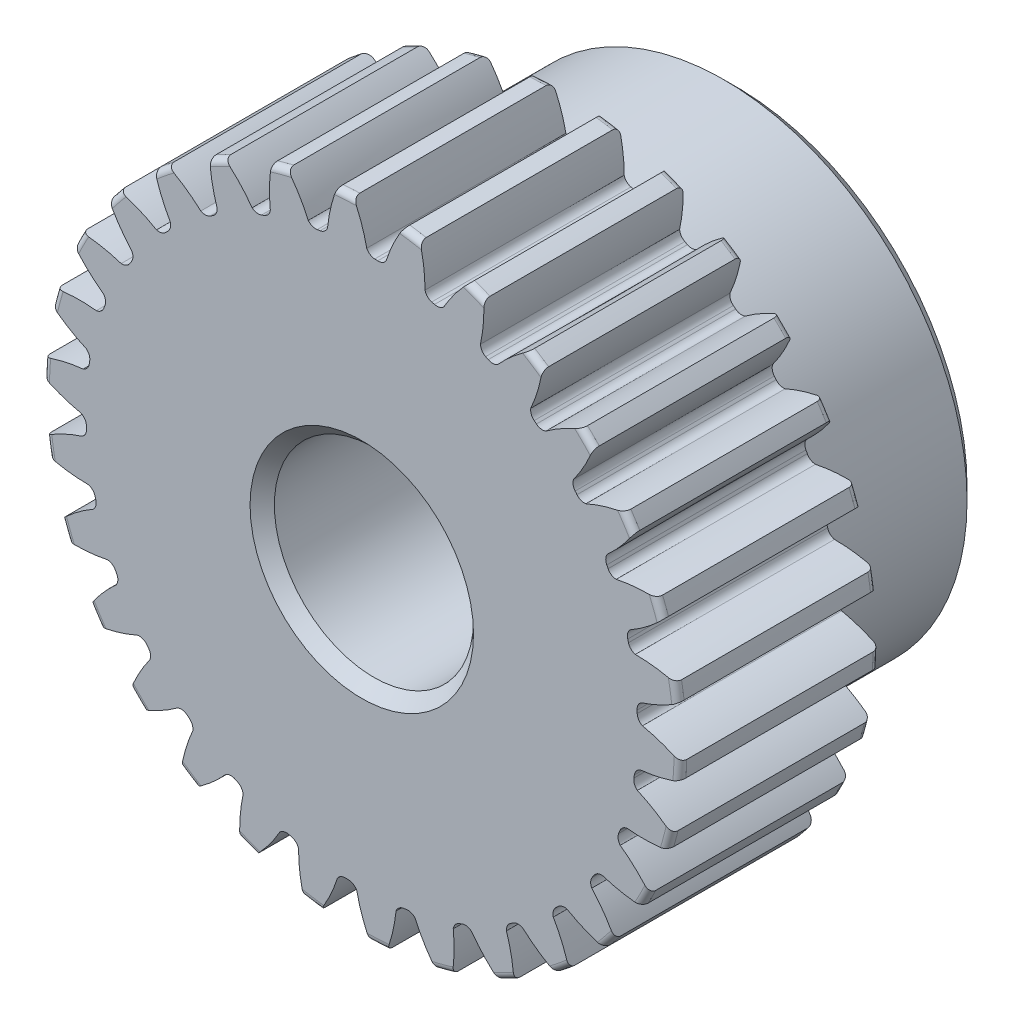
SolidWorks part; units mm, degrees
ref_plane "Front" through (0, 0, 0) normal (0, 0, 1) x (1, 0, 0)
ref_plane "Top" through (0, 0, 0) normal (0, 1, 0) x (1, 0, 0)
ref_plane "Right" through (0, 0, 0) normal (1, 0, 0) x (0, 0, -1)
sketch "Sketch1" plane through (0, 0, 0) normal (0, 0, 1) x (1, 0, 0)
  line L0 (-381, 0) -> (381, 0) construction
  circle A0 centre (0, 0) radius 20.32
  circle A1 centre (0, 0) radius 19.05 construction
  circle A3 centre (0, 0) radius 17.5806 construction
  dimension "D1" = 1.4694
  dimension "D2" = 2.7394
  dimension "D3" = 1.27
extrude "Boss-Extrude1" add sketch "Sketch1" against normal blind 12.7
sketch "Sketch2" plane through (0, 0, 0) normal (1, 0, 0) x (0, 0, -1)
  line L0 (12.7, 0) -> (23.876, 0)
  line L1 (12.7, 0) -> (12.7, 15.494)
  line L2 (12.7, 15.494) -> (23.876, 15.494)
  line L3 (23.876, 15.494) -> (23.876, 0)
  point P5 (23.876, -15.494)
  point P6 (0, -20.32)
  point P7 (12.7, -20.32)
  point P9 (0, 20.32)
revolve "Revolve1" add sketch "Sketch2" angle 360 mid plane about L0
fillet "Fillet2" radius 0.4064 3 edges at (20.32, 0, -12.7) (20.32, 0, 0) (15.494, 0, -12.7)
sketch "Sketch3" plane through (0, 0, 0) normal (0, 0, 1) x (1, 0, 0)
  line L0 (0, 0) -> (0, 20.32) construction
  line L1 (-6.1226, 16.8216) -> (0, 19.05)
  line L2 (-9.5921, 19.05) -> (9.5921, 19.05) construction
  line L3 (-9.0136, 15.7693) -> (9.0136, 22.3307) construction
  line L4 (-6.1226, 16.8216) -> (0, 0) construction
  line L5 (-14.9265, 9.8818) -> (0, 0) construction
  line L6 (-14.9265, 9.8818) -> (-5.0357, 24.822) construction
  line L7 (-4.253, 17.3886) -> (0, 0) construction
  line L8 (-4.253, 17.3886) -> (0.1773, 18.4722) construction
  arc A0 (-6.1226, 16.8216) -> (-14.9265, 9.8818) centre (0, 0) ccw
  circle A1 centre (0, 0) radius 19.05 construction
  circle A2 centre (0, 0) radius 17.9011 construction
  arc A3 (-6.1226, 16.8216) -> (-4.253, 17.3886) centre (0, 0) cw
  circle A4 centre (0, 0) radius 20.32 construction
  point P6 (0, 19.05)
  dimension "D1" = 6.5155
  dimension "D3" = 17.9176
  dimension "D5" = 4.5608
  dimension "D2" = 11.4021
  dimension "D4" = 1.9546
sketch "Sketch4" plane through (0, 0, 0) normal (0, 0, 1) x (1, 0, 0)
  line L0 (0, 0) -> (0.9956, 18.9978) construction
  line L1 (0.3162, 17.8984) -> (0.3162, 17.5778)
  line L2 (0, 19.05) -> (1.9913, 18.9456) construction
  line L3 (1.5564, 17.8334) -> (1.5229, 17.5145)
  line L4 (0.3162, 17.5778) -> (0, 0) construction
  line L5 (0, 0) -> (0, 20.32) construction
  line L6 (-14.9265, 9.8818) -> (-5.0357, 24.822) construction
  line L7 (-14.9265, 9.8818) -> (-5.0357, 24.822) construction
  arc A0 (1.5229, 17.5145) -> (0.3162, 17.5778) centre (0, 0) ccw
  arc A1 (0, 19.05) -> (1.9913, 18.9456) centre (0, 0) cw construction
  circle A2 centre (0, 0) radius 19.05 construction
  circle A3 centre (0, 0) radius 17.9011 construction
  circle A4 centre (0, 0) radius 17.5806 construction
  arc A5 (7.6027, 24.1597) -> (-5.0357, 24.822) centre (0, 0) ccw
  spline S0 degree 2 poles (-5.0357, 24.822) (-0.6022, 22.2364) (0.3162, 17.8984) knots 0 0 0 1 1 1
  spline S1 degree 2 poles (7.6027, 24.1597) (2.9233, 22.0516) (1.5564, 17.8334) knots 0 0 0 1 1 1
  dimension "D1" = 1.9949
extrude "Cut-Extrude1" cut sketch "Sketch4" against normal through all
fillet "Fillet1" radius 0.5985 2 edges at (1.5229, 17.5145, -6.35) (0.3162, 17.5778, -6.35)
pattern_circular "CirPattern1" count 30 over 360 about axis through (0, 0, -12.7) along (0, 0, 1) of "Cut-Extrude1", "Fillet1"
sketch "Sketch5" plane through (0, 0, 0) normal (0, 0, 1) x (1, 0, 0)
  circle A0 centre (0, 0) radius 6.35
  circle A1 centre (0, 0) radius 6.35 construction
  dimension "Bore Min" = 12.7
  dimension "Bore Max" = 12.7
extrude "Cut-Extrude2" cut sketch "Sketch5" against normal through all
chamfer "Chamfer1" distance 0.7747 angle 45 3 edges at (15.494, 0, -23.876) (6.35, 0, 0) (6.35, 0, -23.876)
sketch "Pitch Dia" plane through (0, 0, 0) normal (0, 0, 1) x (1, 0, 0)
  circle A0 centre (0, 0) radius 19.05 construction
  circle A1 centre (0, 0) radius 19.05 construction
equation "\"D1@Boss-Extrude1\" = \"Face Wd@Sketch2\""
equation "\"D2@Sketch3\" = \"D1@Sketch3\"*1.75"
equation "\"D3@Sketch3\" = \"D1@Sketch3\"+\"D2@Sketch3\""
equation "\"D4@Sketch3\" = \"D1@Sketch3\"*.3"
equation "\"D5@Sketch3\" = \"D1@Sketch3\"-\"D4@Sketch3\""
equation "\"D1@Sketch4\" = 1.5708/(\"Number of Teeth@Sketch1\"/\"Ptich Dia@Sketch1\")"
equation "\"D1@Chamfer1\" = \"B Hub Dia@Sketch2\"*.025"
equation "\"D1@CirPattern1\" = \"Number of Teeth@Sketch1\""
equation "\"D1@Fillet1\" = \"D1@Sketch4\"*.3"
equation "\"D1@Fillet2\" = \"OD@Sketch1\"*.01"
equation "\"D1@Sketch1\" = 1.157/(\"Number of Teeth@Sketch1\"/\"Ptich Dia@Sketch1\")"
